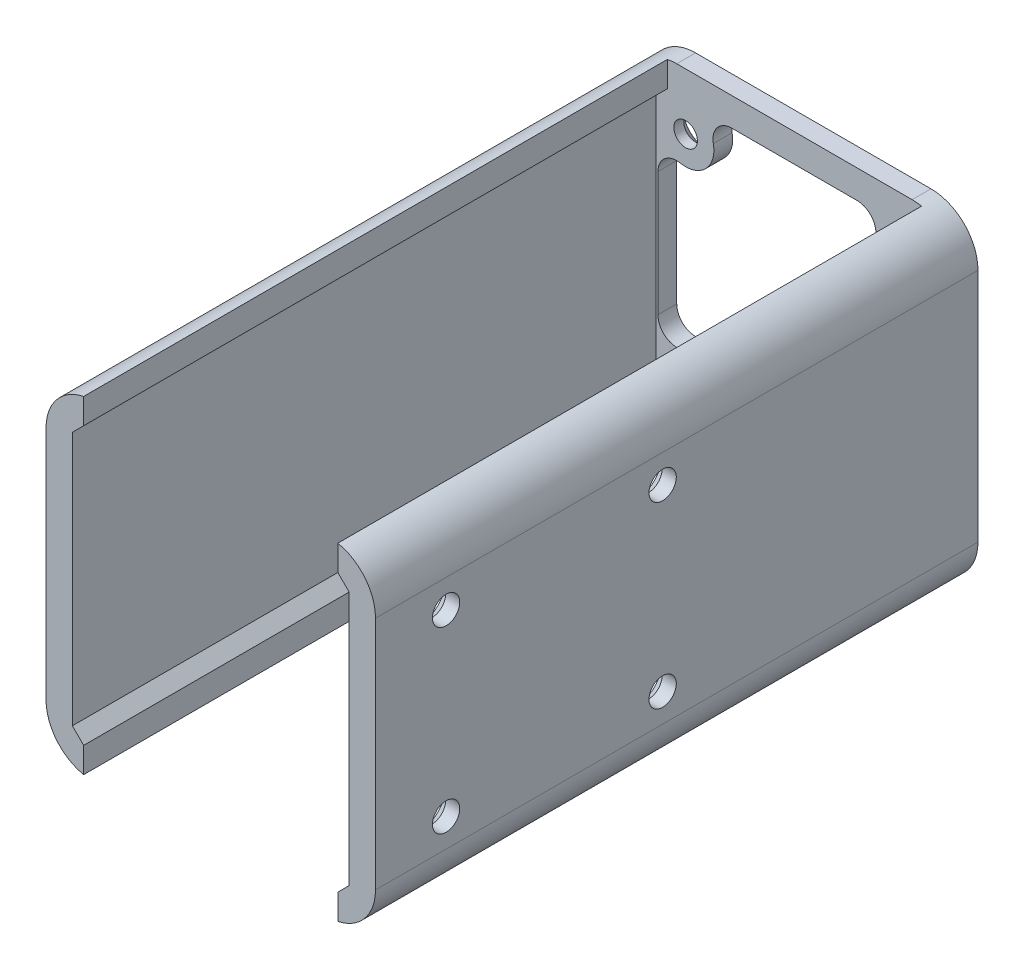
SolidWorks part; units mm, degrees
ref_plane "Front Plane" through (0, 0, 0) normal (0, 0, 1) x (1, 0, 0)
ref_plane "Top Plane" through (0, 0, 0) normal (0, 1, 0) x (1, 0, 0)
ref_plane "Right Plane" through (0, 0, 0) normal (1, 0, 0) x (0, 0, -1)
sketch "Sketch1" plane through (0, 0, 0) normal (0, 0, 1) x (1, 0, 0)
  line L0 (-17.5, 17.5) -> (17.5, 17.5)
  line L1 (11.557, -11.5) -> (-11.557, -11.5) construction
  line L2 (11.557, -11.5) -> (11.557, 11.5) construction
  line L3 (11.557, 11.5) -> (-11.557, 11.5) construction
  line L4 (-11.557, -11.5) -> (-11.557, 11.5) construction
  line L5 (11.557, -11.5) -> (-11.557, 11.5) construction
  line L6 (11.557, 11.5) -> (-11.557, -11.5) construction
  line L7 (-10.3151, -14.5) -> (10.3151, -14.5)
  line L8 (-14.5, -10.2044) -> (-14.5, 10.2044)
  line L9 (-10.3151, 14.5) -> (10.3151, 14.5)
  line L10 (14.5, -10.2044) -> (14.5, 10.2044)
  line L11 (-14.5, -14.5) -> (14.5, 14.5) construction
  line L12 (-14.5, 14.5) -> (14.5, -14.5) construction
  line L13 (17.5, -17.5) -> (17.5, 17.5)
  line L14 (-17.5, -17.5) -> (17.5, -17.5)
  line L15 (-17.5, -17.5) -> (-17.5, 17.5)
  line L16 (-14.5, 14.5) -> (-11.557, 11.5) construction
  line L17 (-10.3151, 14.5) -> (-9.3959, 13.5808)
  line L18 (-14.5, 10.2044) -> (-13.5835, 9.288)
  line L19 (-14.5, 14.5) -> (14.5, 14.5) construction
  line L20 (-14.5, -14.5) -> (-14.5, 14.5) construction
  line L21 (0, 0) -> (0, 11.5) construction
  line L22 (14.5, 10.2044) -> (13.5835, 9.288)
  line L23 (10.3151, 14.5) -> (9.3959, 13.5808)
  line L24 (14.5, -14.5) -> (14.5, 14.5) construction
  line L25 (-11.557, 0) -> (0, 0) construction
  line L26 (-10.3151, -14.5) -> (-9.3959, -13.5808)
  line L27 (-14.5, -10.2044) -> (-13.5835, -9.288)
  line L28 (14.5, -10.2044) -> (13.5835, -9.288)
  line L29 (10.3151, -14.5) -> (9.3959, -13.5808)
  line L30 (-14.5, -14.5) -> (14.5, -14.5) construction
  circle A0 centre (-11.557, 11.5) radius 1.25
  circle A1 centre (11.557, 11.5) radius 1.25
  circle A2 centre (11.557, -11.5) radius 1.25
  circle A3 centre (-11.557, -11.5) radius 1.25
  arc A9 (-13.5835, 9.288) -> (-9.3959, 13.5808) centre (-11.557, 11.5) ccw
  arc A10 (13.5835, 9.288) -> (9.3959, 13.5808) centre (11.557, 11.5) cw
  arc A11 (13.5835, -9.288) -> (9.3959, -13.5808) centre (11.557, -11.5) ccw
  arc A12 (-13.5835, -9.288) -> (-9.3959, -13.5808) centre (-11.557, -11.5) cw
  point P0 (0, 0)
  point P14 (0, 0)
  point P24 (-14.5, 14.5)
  dimension "D3" = 2.5
  dimension "D4" = 3
  dimension "D1" = 23.114
  dimension "D2" = 23
  dimension "D5" = 29
  dimension "D6" = 29
  dimension "D8" = 1.2961
  dimension "D9" = 45
  dimension "D10" = 45
  dimension "D11" = 1.3
  dimension "D7" = 3
extrude "Boss-Extrude1" add sketch "Sketch1" along normal blind 2
sketch "Sketch2" plane through (0, 0, 2) normal (0, 0, 1) x (1, 0, 0)
  line L0 (-13.5, 17.5) -> (-17.5, 17.5)
  line L1 (17.5, 17.5) -> (-17.5, 17.5) construction
  line L2 (-17.5, 17.5) -> (-17.5, 13.5)
  line L3 (-17.5, 17.5) -> (-17.5, -17.5) construction
  line L7 (-13.5, 14.7) -> (-13.5, 17.5)
  line L8 (0, 0) -> (0, 17.5) construction
  line L9 (0, 0) -> (17.5, 0) construction
  line L10 (17.5, -17.5) -> (17.5, 17.5) construction
  line L11 (13.5, 14.7) -> (13.5, 17.5)
  line L15 (17.5, 17.5) -> (17.5, 13.5)
  line L16 (13.5, 17.5) -> (17.5, 17.5)
  line L17 (13.5, -17.5) -> (17.5, -17.5)
  line L18 (17.5, -17.5) -> (17.5, -13.5)
  line L22 (13.5, -14.7) -> (13.5, -17.5)
  line L23 (-13.5, -14.7) -> (-13.5, -17.5)
  line L27 (-17.5, -17.5) -> (-17.5, -13.5)
  line L28 (-13.5, -17.5) -> (-17.5, -17.5)
  line L29 (-14.7, 13.5) -> (-13.5, 14.7)
  line L30 (-14.7, -13.5) -> (-13.5, -14.7)
  line L31 (14.7, -13.5) -> (13.5, -14.7)
  line L33 (14.7, 13.5) -> (13.5, 14.7)
  line L36 (17.5, 13.5) -> (17.5, -13.5)
  line L38 (14.7, 13.5) -> (14.7, -13.5)
  line L40 (-17.5, 13.5) -> (-17.5, -13.5)
  line L42 (-14.7, 13.5) -> (-14.7, -13.5)
  dimension "D1" = 2.8
  dimension "D2" = 2.8
  dimension "D3" = 4
  dimension "D4" = 4
extrude "Boss-Extrude2" add sketch "Sketch2" along normal blind 62
sketch "Sketch3" plane through (0, 0, 0) normal (0, 0, -1) x (-1, 0, 0)
  circle A0 centre (-11.557, 11.5) radius 1.25
  circle A1 centre (11.557, 11.5) radius 1.25
  circle A2 centre (11.557, -11.5) radius 1.25
  circle A3 centre (-11.557, -11.5) radius 1.25
  point P0 (-11.557, 11.5)
  point P3 (11.557, 11.5)
  point P6 (11.557, -11.5)
  point P9 (-11.557, -11.5)
hole_wizard "CSK for M2 Flat Head Machine Screw1" positions "Sketch3" profile "Sketch4" countersink size "M2" standard "ANSI Metric" end condition up to next
sketch "Sketch4" plane through (11.557, 11.5, 0) normal (1, 0, 0) x (0, 1, 0)
  line L0 (0, 0) -> (0, 64)
  line L1 (0, 64) -> (1.2, 64)
  line L2 (1.2, 64) -> (1.2, 1)
  line L3 (1.2, 1) -> (2.2, 0)
  line L5 (2.2, 0) -> (0, 0)
  line L6 (-1.2, 1) -> (-2.2, 0) construction
  line L11 (0, -6.35) -> (0, 107.95) construction
  dimension "Thru Hole Dia." = 2.4
  dimension "Thru Hole Depth" = 64
  dimension "Near C'Sink Dia." = 4.4
  dimension "Near C'Sink Angle" = 90
fillet "Fillet1" radius 5 4 edges at (17.5, -17.5, 32) (-17.5, -17.5, 32) (-17.5, 17.5, 32) (17.5, 17.5, 32)
fillet "Fillet2" radius 2 8 edges at (-10.3151, -14.5, 1) (-14.5, -10.2044, 1) (10.3151, -14.5, 1) (14.5, -10.2044, 1) (14.5, 10.2044, 1) (10.3151, 14.5, 1) (-14.5, 10.2044, 1) (-10.3151, 14.5, 1)
sketch "Sketch5" plane through (14.7, 0, 0) normal (-1, 0, 0) x (0, 0, 1)
  line L0 (64, -13.5) -> (2, -13.5) construction
  line L6 (56.5, 9.5) -> (56.5, -9.5) construction
  line L9 (33.5, 9.5) -> (56.5, 9.5) construction
  line L11 (33.5, 9.5) -> (33.5, -9.5) construction
  line L15 (64, 12.5) -> (64, -12.5) construction
  circle A0 centre (33.5, 9.5) radius 1.2
  circle A1 centre (56.5, 9.5) radius 1.2
  circle A2 centre (56.5, -9.5) radius 1.2
  circle A3 centre (33.5, -9.5) radius 1.2
  point P0 (33.5, 9.5)
  point P2 (56.5, 9.5)
  point P4 (56.5, -9.5)
  point P6 (33.5, -9.5)
  dimension "D7" = 2.4
  dimension "D1" = 23
  dimension "D2" = 19
  dimension "D3" = 4
  dimension "D4" = 4
  dimension "D5" = 19
  dimension "D6" = 23
  dimension "D8" = 7.5
hole_wizard "CSK for M2.5 Flat Head Machine Screw1" positions "Sketch5" profile "Sketch7" countersink size "M2.5" standard "ANSI Metric" end condition up to next
sketch "Sketch7" plane through (14.7, 9.5, 33.5) normal (0, 1, 0) x (0, 0, 1)
  line L0 (0, 0) -> (0, 2.8)
  line L1 (0, 2.8) -> (1.45, 2.8)
  line L2 (1.45, 2.8) -> (1.45, 1.3)
  line L3 (1.45, 1.3) -> (2.75, 0)
  line L5 (2.75, 0) -> (0, 0)
  line L6 (-1.45, 1.3) -> (-2.75, 0) construction
  line L11 (0, -6.35) -> (0, 107.95) construction
  dimension "Thru Hole Dia." = 2.9
  dimension "Thru Hole Depth" = 2.8
  dimension "Near C'Sink Dia." = 5.5
  dimension "Near C'Sink Angle" = 90
